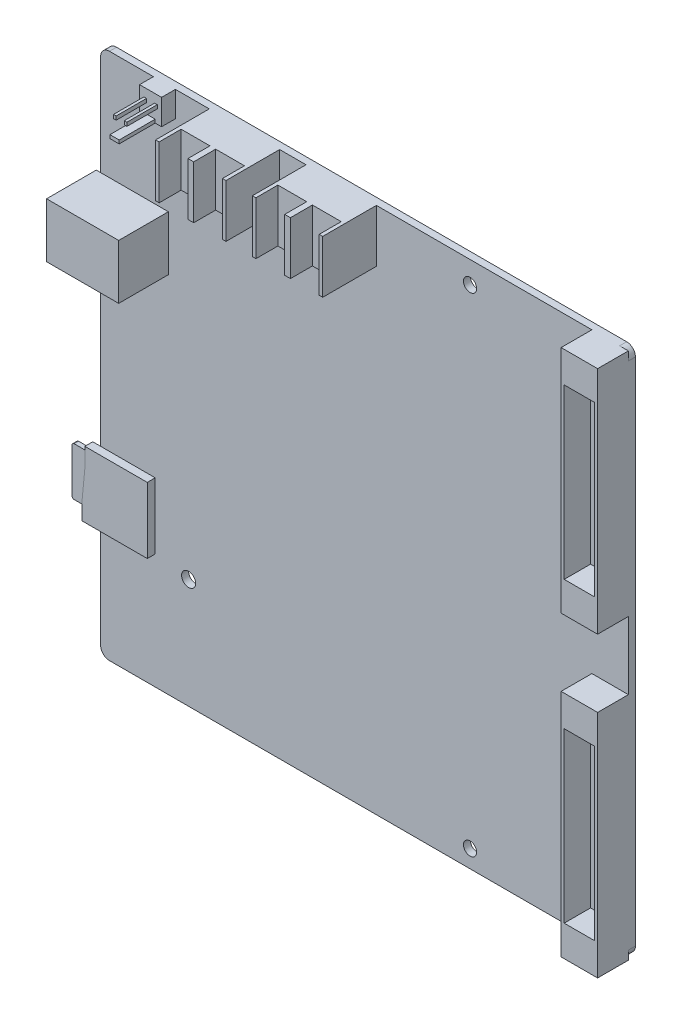
SolidWorks part; units mm, degrees
ref_plane "前视基准面" through (0, 0, 0) normal (0, 0, 1) x (1, 0, 0)
ref_plane "上视基准面" through (0, 0, 0) normal (0, 1, 0) x (1, 0, 0)
ref_plane "右视基准面" through (0, 0, 0) normal (1, 0, 0) x (0, 0, -1)
sketch "草图1" plane through (0, 0, 0) normal (0, 0, 1) x (1, 0, 0)
  line L0 (0, 0) -> (0, 50000) construction
  line L1 (58, -60) -> (-58, -60)
  line L2 (60, -58) -> (60, 58)
  line L3 (58, 60) -> (-58, 60)
  line L4 (-60, -58) -> (-60, 58)
  line L5 (60, -60) -> (-60, 60) construction
  line L6 (60, 60) -> (-60, -60) construction
  line L7 (0, 0) -> (50000, 0) construction
  arc A0 (-58, -60) -> (-60, -58) centre (-58, -58) cw
  arc A1 (58, -60) -> (60, -58) centre (58, -58) ccw
  arc A2 (60, 58) -> (58, 60) centre (58, 58) ccw
  arc A3 (-58, 60) -> (-60, 58) centre (-58, 58) ccw
  circle A5 centre (24, 55) radius 1.5
  circle A6 centre (24, -56) radius 1.5
  point P0 (0, 0)
  dimension "D3" = 2
  dimension "D4" = 4
  dimension "D5" = 36
  dimension "D6" = 5
  dimension "D1" = 120
  dimension "D2" = 120
  dimension "D7" = 36
extrude "凸台-拉伸1" add sketch "草图1" along normal blind 1.6
sketch "草图2" plane through (0, 0, 1.6) normal (0, 0, 1) x (1, 0, 0)
  line L0 (58, 60) -> (-58, 60) construction
  line L1 (-61, 35.1) -> (-44.6, 35.1)
  line L2 (-61, 35.1) -> (-61, 22.7)
  line L3 (-61, 22.7) -> (-44.6, 22.7)
  line L4 (-44.6, 35.1) -> (-44.6, 22.7)
  line L5 (-60, 58) -> (-60, -58) construction
  dimension "D1" = 24.9
  dimension "D2" = 12.4
  dimension "D3" = 1
  dimension "D4" = 16.4
extrude "凸台-拉伸2" add sketch "草图2" along normal blind 11.3
sketch "草图3" plane through (-61, 0, 0) normal (-1, 0, 0) x (0, 0, 1)
  line L0 (12.9, 28.9) -> (50012.9, 28.9) construction
  line L1 (12.9, 35.1) -> (12.9, 22.7) construction
  line L2 (3, 33.7) -> (3, 24.1)
  line L3 (3, 24.1) -> (9.9, 24.1)
  line L4 (9.9, 24.1) -> (11.5, 25.7)
  line L5 (11.5, 25.7) -> (11.5, 32.1)
  line L6 (11.5, 32.1) -> (9.9, 33.7)
  line L7 (9.9, 33.7) -> (3, 33.7)
  line L8 (12.9, 35.1) -> (1.6, 35.1) construction
  line L9 (1.6, 35.1) -> (1.6, 22.7) construction
  line L11 (5.4, 31.6) -> (8.4, 31.6)
  line L12 (5.4, 31.6) -> (5.4, 26.2)
  line L13 (5.4, 26.2) -> (8.4, 26.2)
  line L14 (8.4, 31.6) -> (8.4, 26.2)
  point P4 (12.9, 28.9)
  dimension "D1" = 1.4
  dimension "D2" = 1.4
  dimension "D3" = 1.4
  dimension "D4" = 1.6
  dimension "D5" = 45
  dimension "D6" = 3
  dimension "D7" = 5.4
  dimension "D8" = 2.4
extrude "切除-拉伸1" cut sketch "草图3" against normal blind 9
sketch "草图4" plane through (0, 0, 1.6) normal (0, 0, 1) x (1, 0, 0)
  line L0 (-47.6, -18.8) -> (-47.6, -33.8)
  line L1 (-47.6, -33.8) -> (-62.4, -33.8)
  line L2 (-62.4, -33.8) -> (-62.4, -29.5)
  line L3 (-62.4, -29.5) -> (-61.8, -23.1886)
  line L4 (-61.8, -23.1886) -> (-61.8, -18.8)
  line L5 (-61.8, -18.8) -> (-47.6, -18.8)
  line L6 (-58, -60) -> (58, -60) construction
  line L7 (-60, 22.7) -> (-60, -58) construction
  dimension "D1" = 15
  dimension "D2" = 26.2
  dimension "D3" = 14.8
  dimension "D4" = 2.4
  dimension "D5" = 14.2
  dimension "D6" = 4.3
extrude "凸台-拉伸3" add sketch "草图4" along normal blind 1.8
sketch "草图5" plane through (-61.8, 0, 0) normal (-1, 0, 0) x (0, 0, 1)
  line L0 (3.4, -18.8) -> (3.4, -23.1886) construction
  line L1 (3.3, -19.6) -> (2.3, -19.6)
  line L2 (3.3, -19.6) -> (3.3, -30.6)
  line L3 (3.3, -30.6) -> (2.3, -30.6)
  line L4 (2.3, -19.6) -> (2.3, -30.6)
  line L5 (3.4, -18.8) -> (1.6, -18.8) construction
  dimension "D1" = 0.1
  dimension "D2" = 0.8
  dimension "D3" = 1
  dimension "D4" = 11
extrude "凸台-拉伸4" add sketch "草图5" along normal blind 3
fillet "圆角1" radius 0.5 2 edges at (-64.8, -19.6, 2.8) (-64.8, -30.6, 2.8)
sketch "草图29" [suppressed] plane through (67.7702, 21.0857, 8.6) normal (0, 0, 1) x (1, 0, 0)
  line L0 (-20.6702, -71.8857) -> (-14.8702, -71.8857) construction
  line L1 (-15.5702, -71.1857) -> (-19.9702, -71.1857)
  line L2 (-15.5702, -71.1857) -> (-15.5702, -59.9857)
  line L3 (-15.5702, -59.9857) -> (-19.9702, -59.9857)
  line L4 (-19.9702, -71.1857) -> (-19.9702, -59.9857)
  line L5 (-14.8702, -59.2857) -> (-20.6702, -59.2857) construction
  line L6 (-14.8702, -71.8857) -> (-14.8702, -59.2857) construction
  line L7 (-20.6702, -59.2857) -> (-20.6702, -71.8857) construction
  dimension "D1" = 0.7
  dimension "D2" = 0.7
  dimension "D3" = 0.7
  dimension "D4" = 0.7
extrude "切除-拉伸8" [suppressed] cut sketch "草图29" against normal blind 6
sketch "草图31" [suppressed] plane through (67.7702, 21.0857, 8.6) normal (0, 0, 1) x (1, 0, 0)
  line L1 (-18.6702, -71.8857) -> (-19.9702, -71.8857)
  line L2 (-18.6702, -71.8857) -> (-18.6702, -71.1857)
  line L3 (-18.6702, -71.1857) -> (-19.9702, -71.1857)
  line L4 (-19.9702, -71.8857) -> (-19.9702, -71.1857)
  line L5 (-19.9702, -71.1857) -> (-15.5702, -71.1857) construction
  line L7 (-20.6702, -61.4857) -> (-20.6702, -62.6857)
  line L8 (-19.9702, -62.6857) -> (-20.6702, -62.6857)
  line L9 (-19.9702, -61.4857) -> (-19.9702, -62.6857)
  line L10 (-19.9702, -61.4857) -> (-20.6702, -61.4857)
  line L12 (-19.9702, -59.9857) -> (-19.9702, -71.1857) construction
  line L13 (-19.9702, -69.6857) -> (-20.6702, -69.6857)
  line L14 (-19.9702, -69.6857) -> (-19.9702, -68.4857)
  line L15 (-19.9702, -68.4857) -> (-20.6702, -68.4857)
  line L16 (-20.6702, -69.6857) -> (-20.6702, -68.4857)
  line L17 (-20.6702, -59.2857) -> (-20.6702, -71.8857) construction
  line L19 (-19.9702, -59.2857) -> (-19.9702, -59.9857)
  line L20 (-18.6702, -59.9857) -> (-19.9702, -59.9857)
  line L21 (-18.6702, -59.2857) -> (-18.6702, -59.9857)
  line L22 (-18.6702, -59.2857) -> (-19.9702, -59.2857)
  line L23 (-30.8, -65.5857) -> (49969.2, -65.5857) construction
  line L24 (-14.8702, -71.8857) -> (-14.8702, -59.2857) construction
  line L26 (-14.8702, -71.8857) -> (-14.8702, -59.2857) construction
  line L27 (-20.6702, -71.8857) -> (-14.8702, -71.8857) construction
  point P34 (-14.8702, -65.5857)
  dimension "D1" = 3.8
  dimension "D2" = 2.2
  dimension "D4" = 1.2
extrude "切除-拉伸9" [suppressed] cut sketch "草图31" against normal blind 3
sketch "草图33" [suppressed] plane through (67.7702, 21.0857, 2.6) normal (0, 0, 1) x (1, 0, 0)
  line L0 (-30.8, -65.5857) -> (49969.2, -65.5857) construction
  line L1 (-14.8702, -71.8857) -> (-14.8702, -59.2857) construction
  line L2 (-17.8702, -45.785) -> (-17.8702, 49954.215) construction
  line L3 (-20.6702, -59.2857) -> (-20.6702, -71.8857) construction
  line L4 (-17.8702, -63.9357) -> (-17.8702, -64.7357)
  line L5 (-17.8702, -61.4357) -> (-18.6702, -61.4357)
  line L6 (-17.8702, -61.4357) -> (-17.8702, -62.2357)
  line L7 (-17.8702, -62.2357) -> (-18.6702, -62.2357)
  line L8 (-18.6702, -61.4357) -> (-18.6702, -62.2357)
  line L9 (-17.8702, -63.9357) -> (-18.6702, -63.9357)
  line L10 (-18.6702, -63.9357) -> (-18.6702, -64.7357)
  line L11 (-17.8702, -64.7357) -> (-18.6702, -64.7357)
  line L12 (-17.8702, -66.4357) -> (-17.8702, -67.2357)
  line L13 (-17.8702, -66.4357) -> (-18.6702, -66.4357)
  line L14 (-18.6702, -66.4357) -> (-18.6702, -67.2357)
  line L15 (-17.8702, -67.2357) -> (-18.6702, -67.2357)
  line L16 (-17.8702, -68.9357) -> (-17.8702, -69.7357)
  line L17 (-17.8702, -68.9357) -> (-18.6702, -68.9357)
  line L18 (-18.6702, -68.9357) -> (-18.6702, -69.7357)
  line L19 (-17.8702, -69.7357) -> (-18.6702, -69.7357)
  line L20 (-17.8702, -61.4357) -> (-17.8702, -63.9357) construction
  point P4 (-14.8702, -65.5857)
  dimension "D1" = 2.8
  dimension "D2" = 0.8
  dimension "D3" = 0.8
  dimension "D5" = 2.5
  dimension "D4" = 4
extrude "凸台-拉伸12" [suppressed] add sketch "草图33" along normal blind 4.5 and the other way blind 4
sketch "草图43" plane through (66.8909, 85.5626, 1.6) normal (0, 0, 1) x (1, 0, 0)
  line L0 (-6.8909, -143.5626) -> (-6.8909, -27.5626) construction
  line L1 (-15.1909, -77.8626) -> (-6.8909, -77.8626)
  line L2 (-15.1909, -77.8626) -> (-15.1909, -25.5626)
  line L3 (-15.1909, -25.5626) -> (-6.8909, -25.5626)
  line L4 (-6.8909, -77.8626) -> (-6.8909, -25.5626)
  line L5 (-8.8909, -25.5626) -> (-124.8909, -25.5626) construction
  line L6 (-6.8909, -93.2626) -> (-15.1909, -93.2626)
  line L7 (-15.1909, -93.2626) -> (-15.1909, -145.5626)
  line L8 (-15.1909, -145.5626) -> (-6.8909, -145.5626)
  line L9 (-6.8909, -145.5626) -> (-6.8909, -93.2626)
  line L10 (-124.8909, -145.5626) -> (-8.8909, -145.5626) construction
  dimension "D1" = 8.3
  dimension "D2" = 52.3
  dimension "D3" = 0
  dimension "D4" = 52.3
  dimension "D5" = 8.3
  dimension "D6" = 0
extrude "凸台-拉伸15" add sketch "草图43" along normal blind 7
sketch "草图45" plane through (66.8909, 85.5626, 8.6) normal (0, 0, 1) x (1, 0, 0)
  line L0 (-15.1909, -77.8626) -> (-6.8909, -77.8626) construction
  line L1 (-7.5909, -70.8626) -> (-14.4909, -70.8626)
  line L2 (-7.5909, -70.8626) -> (-7.5909, -32.5626)
  line L3 (-7.5909, -32.5626) -> (-14.4909, -32.5626)
  line L4 (-14.4909, -70.8626) -> (-14.4909, -32.5626)
  line L5 (-6.8909, -25.5626) -> (-15.1909, -25.5626) construction
  line L6 (-6.8909, -77.8626) -> (-6.8909, -25.5626) construction
  line L7 (-15.1909, -25.5626) -> (-15.1909, -77.8626) construction
  line L8 (-7.5909, -100.2626) -> (-14.4909, -100.2626)
  line L9 (-14.4909, -100.2626) -> (-14.4909, -138.5626)
  line L10 (-14.4909, -138.5626) -> (-7.5909, -138.5626)
  line L11 (-7.5909, -138.5626) -> (-7.5909, -100.2626)
  line L12 (-6.8909, -145.5626) -> (-6.8909, -93.2626) construction
  line L13 (-15.1909, -93.2626) -> (-15.1909, -145.5626) construction
  line L14 (-6.8909, -93.2626) -> (-15.1909, -93.2626) construction
  line L15 (-15.1909, -145.5626) -> (-6.8909, -145.5626) construction
  dimension "D1" = 7
  dimension "D2" = 7
  dimension "D3" = 0.7
  dimension "D4" = 0.7
  dimension "D5" = 0.7
  dimension "D6" = 0.7
  dimension "D7" = 7
  dimension "D8" = 7
extrude "切除-拉伸12" cut sketch "草图45" against normal blind 6
sketch "草图53" plane through (0, 0, 1.6) normal (0, 0, 1) x (1, 0, 0)
  line L0 (51.7, 60) -> (-58, 60) construction
  line L1 (-13.3, 60) -> (2.7, 60)
  line L2 (-13.3, 60) -> (-13.3, 48)
  line L3 (-13.3, 48) -> (2.7, 48)
  line L4 (2.7, 60) -> (2.7, 48)
  line L5 (-60, 58) -> (-60, 35.1) construction
  dimension "D1" = 12
  dimension "D2" = 16
  dimension "D3" = 46.7
extrude "凸台-拉伸20" add sketch "草图53" along normal blind 12.2
sketch "草图54" plane through (0, 0, 13.8) normal (0, 0, 1) x (1, 0, 0)
  line L0 (2.7, 60) -> (-13.3, 60) construction
  line L1 (-12.5, 60) -> (-5.95, 60)
  line L2 (-12.5, 60) -> (-12.5, 48)
  line L3 (-12.5, 48) -> (-5.95, 48)
  line L4 (-5.95, 60) -> (-5.95, 48)
  line L5 (-13.3, 48) -> (2.7, 48) construction
  line L6 (-13.3, 48) -> (2.7, 48) construction
  line L7 (1.9, 60) -> (-4.65, 60)
  line L8 (1.9, 60) -> (1.9, 48)
  line L9 (1.9, 48) -> (-4.65, 48)
  line L10 (-4.65, 60) -> (-4.65, 48)
  line L11 (2.7, 48) -> (2.7, 60) construction
  line L12 (-13.3, 60) -> (-13.3, 48) construction
  line L13 (-5.3, 55) -> (-5.3, 50055) construction
  point P20 (-5.3, 60)
  dimension "D1" = 0.8
  dimension "D2" = 0.8
  dimension "D3" = 1.3
extrude "切除-拉伸14" cut sketch "草图54" against normal blind 5
sketch "草图59" plane through (0, 0, 1.6) normal (0, 0, 1) x (1, 0, 0)
  line L0 (-60, 58) -> (-60, 35.1) construction
  line L1 (-13.3, 60) -> (-58, 60) construction
  line L3 (-60, 22.7) -> (-60, -18.8) construction
  line L4 (-58, -60) -> (51.7, -60) construction
  circle A0 centre (-40, -35) radius 1.6
  circle A1 centre (-40, 45) radius 1.6
  dimension "D1" = 20
  dimension "D2" = 15
  dimension "D3" = 25
  dimension "D4" = 20
extrude "切除-拉伸16" cut sketch "草图59" against normal blind 10
pattern_linear "阵列(线性)4" count 2 spacing 22 along (-1, 0, 0) of "凸台-拉伸20", "切除-拉伸14"
sketch "草图60" plane through (0, 0, 1.6) normal (0, 0, 1) x (1, 0, 0)
  line L0 (-43, 54.2) -> (-43, 60)
  line L1 (-43, 60) -> (-48, 60)
  line L2 (-48, 60) -> (-48, 54.2)
  line L3 (-48, 54.2) -> (-43, 54.2)
  line L4 (-60, 58) -> (-60, 35.1) construction
  line L5 (-35.3, 60) -> (-58, 60) construction
  dimension "D1" = 5.8
  dimension "D2" = 5
  dimension "D3" = 12
extrude "凸台-拉伸21" add sketch "草图60" along normal blind 3.15
sketch "草图61" plane through (0, 0, 4.75) normal (0, 0, 1) x (1, 0, 0)
  line L0 (-44.45, 54.2) -> (-44.45, 54.98)
  line L1 (-48, 54.2) -> (-43, 54.2) construction
  line L2 (-44.45, 54.98) -> (-46.55, 54.98)
  line L3 (-46.55, 54.98) -> (-46.55, 54.2)
  line L5 (-43, 54.2) -> (-43, 60) construction
  line L6 (-44.45, 54.2) -> (-46.55, 54.2)
  dimension "D1" = 0.78
  dimension "D2" = 1.45
  dimension "D3" = 2.1
extrude "凸台-拉伸22" add sketch "草图61" along normal blind 8.2
sketch "草图62" plane through (0, 0, 4.75) normal (0, 0, 1) x (1, 0, 0)
  line L0 (-43.975, 57.2391) -> (-43.975, 58.075)
  line L1 (-43.975, 58.075) -> (-44.575, 58.075)
  line L2 (-44.575, 58.075) -> (-44.575, 57.2391)
  line L3 (-44.575, 57.2391) -> (-43.975, 57.2391)
  line L4 (-46.425, 57.2391) -> (-47.025, 57.2391)
  line L5 (-47.025, 57.2391) -> (-47.025, 58.075)
  line L6 (-47.025, 58.075) -> (-46.425, 58.075)
  line L7 (-46.425, 58.075) -> (-46.425, 57.2391)
  line L8 (-43, 54.2) -> (-43, 60) construction
  dimension "D1" = 0.6
  dimension "D2" = 1.85
  dimension "D3" = 0.975
extrude "凸台-拉伸23" add sketch "草图62" along normal blind 6.9 and the other way blind 6
sketch "草图63" plane through (0, 0, 1.6) normal (0, 0, 1) x (1, 0, 0)
  line L0 (-13.5, -60) -> (-31.5, -60)
  line L1 (-58, -60) -> (51.7, -60) construction
  line L2 (-31.5, -60) -> (-31.5, -29)
  line L3 (-31.5, -29) -> (-13.5, -29)
  line L4 (-13.5, -29) -> (-13.5, -60)
  line L5 (-60, -33.8) -> (-60, -58) construction
  dimension "D1" = 28.5
  dimension "D2" = 18
  dimension "D3" = 31
extrude "凸台-拉伸24" [suppressed] add sketch "草图63" along normal blind 3.3
sketch "草图64" [suppressed] plane through (0, 0, 4.9) normal (0, 0, 1) x (1, 0, 0)
  line L0 (-8.5, -53.5) -> (-21.5, -53.5)
  line L1 (-8.5, -60) -> (-8.5, -29) construction
  line L2 (-21.5, -53.5) -> (-21.5, -50)
  line L3 (-21.5, -50) -> (-26.5, -50)
  line L4 (-26.5, -29) -> (-26.5, -60) construction
  line L5 (-26.5, -50) -> (-26.5, -60)
  line L6 (-26.5, -60) -> (-8.5, -60)
  line L7 (-8.5, -60) -> (-8.5, -53.5)
  dimension "D1" = 6.5
  dimension "D2" = 5
  dimension "D3" = 3.5
extrude "切除-拉伸17" [suppressed] cut sketch "草图64" against normal blind 2.5
sketch "草图65" [suppressed] plane through (0, 0, 2.4) normal (0, 0, 1) x (1, 0, 0)
  circle A0 centre (-24.2463, -52.738) radius 1
  circle A1 centre (-24.2463, -52.738) radius 0.75
  dimension "D1" = 2
  dimension "D2" = 1.5
extrude "凸台-拉伸25" [suppressed] add sketch "草图65" along normal blind 1
